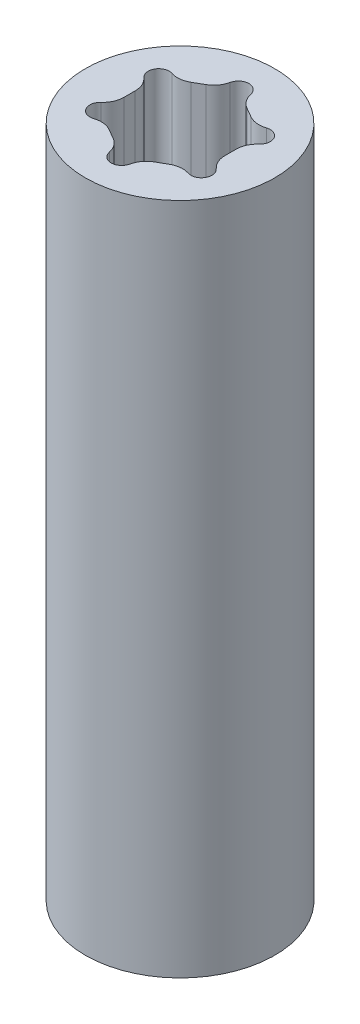
SolidWorks part; units mm, degrees
ref_plane "Front Plane" through (0, 0, 0) normal (0, 0, 1) x (1, 0, 0)
ref_plane "Top Plane" through (0, 0, 0) normal (0, 1, 0) x (1, 0, 0)
ref_plane "Right Plane" through (0, 0, 0) normal (1, 0, 0) x (0, 0, -1)
sketch "Sketch1" plane through (0, 0, 0) normal (0, 1, 0) x (1, 0, 0)
  line L1 (-2.4, 1.3856) -> (-2.4, -1.3856)
  line L2 (-2.4, -1.3856) -> (0, -2.7713)
  line L3 (0, -2.7713) -> (2.4, -1.3856)
  line L4 (2.4, -1.3856) -> (2.4, 1.3856)
  line L5 (2.4, 1.3856) -> (0, 2.7713)
  line L6 (0, 2.7713) -> (-2.4, 1.3856)
  circle A0 centre (0, 0) radius 4.5
  circle A1 centre (0, 0) radius 2.4 construction
  circle A2 centre (0, 2.7713) radius 0.5
  circle A3 centre (0, 0) radius 2.4 construction
  circle A4 centre (2.4, 1.3856) radius 0.5
  circle A5 centre (0, 0) radius 2.4 construction
  circle A6 centre (2.4, -1.3856) radius 0.5
  circle A7 centre (0, 0) radius 2.4 construction
  circle A8 centre (0, -2.7713) radius 0.5
  circle A9 centre (0, 0) radius 2.4 construction
  circle A10 centre (-2.4, -1.3856) radius 0.5
  circle A11 centre (0, 0) radius 2.4 construction
  circle A12 centre (-2.4, 1.3856) radius 0.5
  point P28 (0, 0)
  dimension "D1" = 4.8
  dimension "D2" = 9
  dimension "D3" = 1
  dimension "D4" = 6
extrude "Boss-Extrude1" add sketch "Sketch1" along normal blind 32 contours A0 A12 L6 A2 L5 A4 L4 A6 L3 A8 L2 A10 L1 region at (-4.3727, 0, 0)
extrude "Boss-Extrude2" add sketch "Sketch1<4>" along normal blind 9 contours A0
sketch "Sketch1<4>" plane through (0, 0, 0) normal (0, 1, 0) x (1, 0, 0) same geometry as "Sketch1"
hole_wizard "M3 Clearance Hole1" positions "Sketch2" profile "Sketch3" hole size "M3" standard "ANSI Metric" end condition through all
sketch "Sketch2" plane through (0, 0, 0) normal (0, -1, 0) x (-1, 0, 0)
  point P0 (0, 0)
sketch "Sketch3" plane through (0, 0, 0) normal (1, 0, 0) x (0, 0, -1)
  line L0 (0, 0) -> (0, 32)
  line L1 (0, 32) -> (1.8, 32)
  line L2 (1.8, 32) -> (1.8, 0.025)
  line L3 (1.8, 0.025) -> (1.825, 0)
  line L5 (1.825, 0) -> (0, 0)
  line L6 (-1.8, 0.025) -> (-1.825, 0) construction
  line L11 (0, -6.35) -> (0, 107.95) construction
  dimension "Thru Hole Dia." = 3.6
  dimension "Thru Hole Depth" = 32
  dimension "Near C'Sink Dia." = 3.65
  dimension "Near C'Sink Angle" = 90
fillet "Fillet1" radius 1 12 edges at (-2.4, 20.5, -0.8856) (-2.4, 20.5, 0.8856) (-1.967, 20.5, 1.6356) (-0.433, 20.5, 2.5213) (1.967, 20.5, 1.6356) (2.4, 20.5, 0.8856) (2.4, 20.5, -0.8856) (1.967, 20.5, -1.6356) (0.433, 20.5, -2.5213) (-0.433, 20.5, -2.5213) (-1.967, 20.5, -1.6356) (0.433, 20.5, 2.5213)
